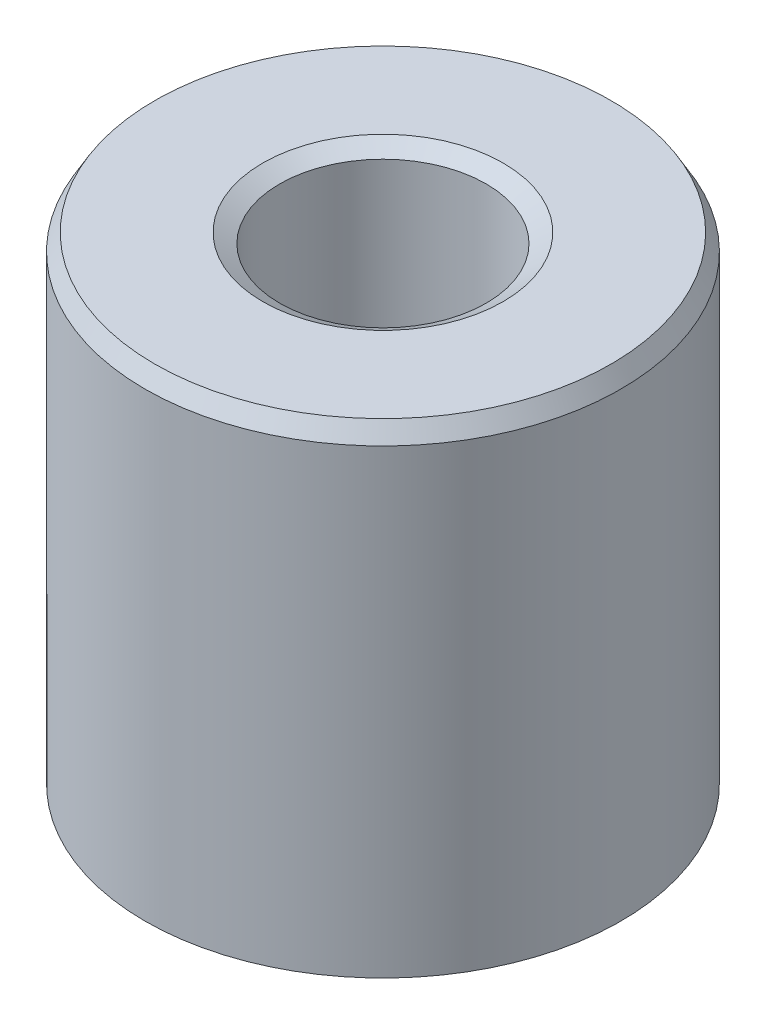
SolidWorks part; units mm, degrees
ref_plane "Front Plane" through (0, 0, 0) normal (0, 0, 1) x (1, 0, 0)
ref_plane "Top Plane" through (0, 0, 0) normal (0, 1, 0) x (1, 0, 0)
ref_plane "Right Plane" through (0, 0, 0) normal (1, 0, 0) x (0, 0, -1)
sketch "Sketch1" plane through (0, 0, 0) normal (0, 1, 0) x (1, 0, 0)
  circle A0 centre (0, 0) radius 32.5
  dimension "SLEEVE_OD" = 65
extrude "Boss-Extrude1" add sketch "Sketch1" along normal blind 66.57
sketch "Sketch2" plane through (0, 0, 0) normal (0, 1, 0) x (1, 0, 0)
  circle A0 centre (0, 0) radius 14.1127
  dimension "BORE_D" = 28.2254
extrude "Cut-Extrude1" cut sketch "Sketch2" along normal through all
chamfer "Chamfer1" distance 2.2995 angle 30 4 edges at (0, 66.57, 14.1127) (0, 0, 14.1127) (0, 0, 32.5) (0, 66.57, 32.5) first distance on face at (0, 66.57, 14.1127) first distance on face at (0, 0, 14.1127) first distance on face at (0, 66.57, 32.5)
